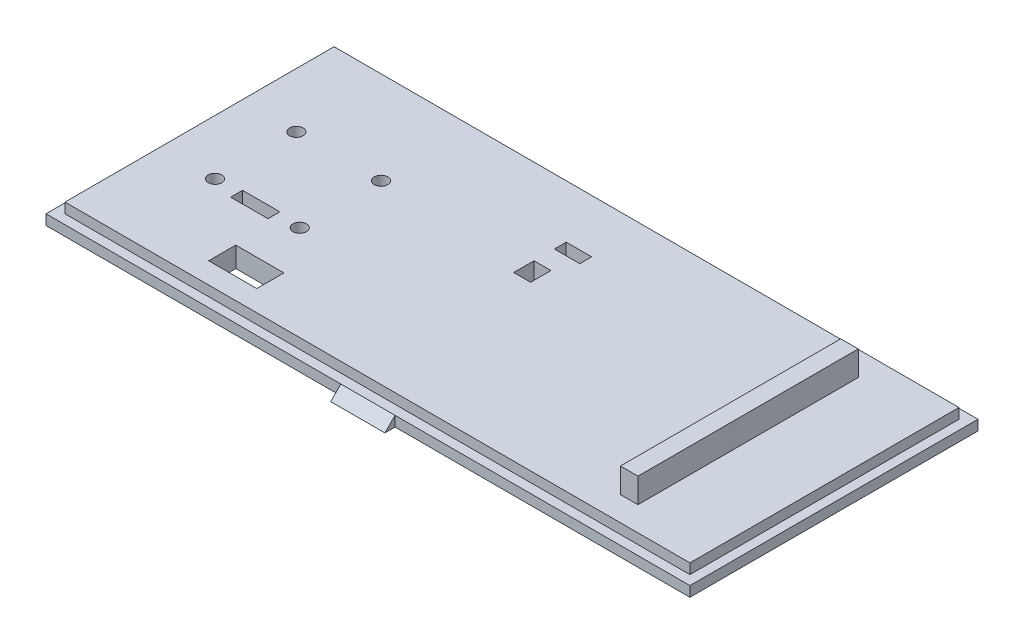
SolidWorks part; units mm, degrees
ref_plane "Front Plane" through (0, 0, 0) normal (0, 0, 1) x (1, 0, 0)
ref_plane "Top Plane" through (0, 0, 0) normal (0, 1, 0) x (1, 0, 0)
ref_plane "Right Plane" through (0, 0, 0) normal (1, 0, 0) x (0, 0, -1)
sketch "Sketch2" plane through (0, 0, 0) normal (0, 1, 0) x (1, 0, 0)
  line L1 (0, 0) -> (-190, 0)
  line L2 (0, 0) -> (0, 85)
  line L3 (0, 85) -> (-190, 85)
  line L4 (-190, 0) -> (-190, 85)
extrude "Boss-Extrude1" add sketch "Sketch2" along normal blind 3
sketch "Sketch6" plane through (0, 3, 0) normal (0, 1, 0) x (1, 0, 0)
  line L0 (-190, 85) -> (-190, 0) construction
  line L1 (-187.2, 82.2) -> (-2.8, 82.2)
  line L2 (-187.2, 82.2) -> (-187.2, 2.8)
  line L3 (-187.2, 2.8) -> (-2.8, 2.8)
  line L4 (-2.8, 82.2) -> (-2.8, 2.8)
  line L5 (0, 85) -> (-190, 85) construction
  line L6 (-55, 0) -> (55, 0) construction
  line L7 (0, -55) -> (0, 55) construction
  dimension "D1" = 2.8
  dimension "D2" = 2.8
  dimension "D3" = 2.8
  dimension "D4" = 2.8
extrude "Boss-Extrude4" add sketch "Sketch6" along normal blind 3
sketch "Sketch8" plane through (0, 3, 0) normal (0, 1, 0) x (1, 0, 0)
  line L0 (-95, 0) -> (-95, 85) construction
  line L1 (-190, 0) -> (0, 0) construction
  line L2 (0, 85) -> (-190, 85) construction
  line L3 (-190, 42.5) -> (0, 42.5) construction
  line L4 (-87, 0) -> (-103, 0)
  line L5 (-95, 0) -> (-95, -3)
  line L6 (-87, -3) -> (-103, -3)
  line L7 (-103, 0) -> (-103, -3)
  line L8 (-190, 85) -> (-190, 0) construction
  line L9 (0, 0) -> (0, 85) construction
  line L10 (-87, 0) -> (-87, -3)
  line L11 (-87, 85) -> (-87, 88)
  line L12 (-87, 85) -> (-103, 85)
  line L13 (-103, 85) -> (-103, 88)
  line L14 (-87, 88) -> (-103, 88)
  dimension "D1" = 8
  dimension "D2" = 3
extrude "Boss-Extrude5" add sketch "Sketch8" against normal blind 3 contours L4 L7 L6 L10 | L14 L13 L12 L11
chamfer "Chamfer2" distance 3 angle 45 2 edges at (-95, 3, 3) (-95, 3, -88)
sketch "Sketch10" plane through (0, 0, 0) normal (0, -1, 0) x (1, 0, 0)
  line L0 (-190, -85) -> (-190, 0) construction
  line L1 (-103, -63) -> (-95.5, -63)
  line L2 (-103, -63) -> (-103, -66.5)
  line L3 (-103, -66.5) -> (-95.5, -66.5)
  line L4 (-95.5, -63) -> (-95.5, -66.5)
  line L5 (-190, 0) -> (-103, 0) construction
  line L6 (-103, -85) -> (-190, -85) construction
  dimension "D1" = 87
  dimension "D2" = 7.5
  dimension "D3" = 3.5
  dimension "D4" = 63
  dimension "D5" = 18.5
extrude "Cut-Extrude1" cut sketch "Sketch10" against normal through all and the other way through all
sketch "Sketch11" plane through (0, 0, 0) normal (0, -1, 0) x (1, 0, 0)
  line L1 (-103, -51) -> (-98, -51)
  line L2 (-103, -51) -> (-103, -57)
  line L3 (-103, -57) -> (-98, -57)
  line L4 (-98, -51) -> (-98, -57)
  line L5 (-190, -85) -> (-190, 0) construction
  line L6 (-103, -63) -> (-95.5, -63) construction
  dimension "D1" = 6
  dimension "D2" = 87
  dimension "D3" = 6
  dimension "D4" = 5
extrude "Cut-Extrude2" cut sketch "Sketch11" against normal through all
sketch "Sketch12" plane through (0, 0, 0) normal (0, -1, 0) x (1, 0, 0)
  line L0 (-190, -85) -> (-190, 0) construction
  line L1 (-164, -32) -> (-153, -32)
  line L2 (-164, -32) -> (-164, -28.5)
  line L3 (-164, -28.5) -> (-153, -28.5)
  line L4 (-153, -32) -> (-153, -28.5)
  line L5 (-190, 0) -> (-103, 0) construction
  line L6 (-158.5, -32) -> (-158.5, 15.5771) construction
  line L7 (-171, -54.8755) -> (-171, 0) construction
  line L8 (-103, -85) -> (-190, -85) construction
  circle A0 centre (-171, -54.8755) radius 2
  circle A1 centre (-171, -30.8755) radius 2
  circle A2 centre (-146, -54.8755) radius 2
  circle A3 centre (-146, -30.8755) radius 2
  dimension "D5" = 7
  dimension "D6" = 24
  dimension "D1" = 26
  dimension "D2" = 32
  dimension "D3" = 3.5
  dimension "D4" = 11
  dimension "D7" = 53
extrude "Cut-Extrude3" cut sketch "Sketch12" against normal through all
sketch "Sketch13" plane through (0, 0, 0) normal (0, -1, 0) x (1, 0, 0)
  line L0 (-190, -85) -> (-190, 0) construction
  line L1 (-151, -9) -> (-136.8, -9)
  line L2 (-151, -9) -> (-151, -17)
  line L3 (-151, -17) -> (-136.8, -17)
  line L4 (-136.8, -9) -> (-136.8, -17)
  line L6 (-103, -85) -> (-190, -85) construction
  dimension "D1" = 39
  dimension "D2" = 68
  dimension "D3" = 14.2
  dimension "D4" = 8
extrude "Cut-Extrude4" cut sketch "Sketch13" against normal through all
sketch "Sketch14" plane through (0, 6, 0) normal (0, 1, 0) x (1, 0, 0)
  line L0 (-51.8, 2.8) -> (-51.8, 82.2)
  line L1 (-187.2, 2.8) -> (-2.8, 2.8) construction
  line L2 (-2.8, 82.2) -> (-187.2, 82.2) construction
  line L3 (-2.8, 2.8) -> (-2.8, 82.2) construction
  line L4 (-51.8, 42.5) -> (-2.8, 42.5) construction
  line L5 (-28.0054, 82.2) -> (-28.0054, 2.8) construction
  line L6 (-2.8, 82.2) -> (-187.2, 82.2) construction
  line L7 (-2.8, 2.8) -> (-2.8, 82.2) construction
  line L8 (-187.2, 2.8) -> (-2.8, 2.8) construction
  line L9 (-30.5054, 8) -> (-25.5054, 8)
  line L10 (-30.5054, 8) -> (-30.5054, 2.8)
  line L11 (-30.5054, 2.8) -> (-25.5054, 2.8)
  line L12 (-25.5054, 8) -> (-25.5054, 2.8)
  line L13 (-30.5054, 82.2) -> (-25.5054, 82.2)
  line L14 (-25.5054, 77) -> (-25.5054, 82.2)
  line L15 (-30.5054, 77) -> (-30.5054, 82.2)
  line L16 (-30.5054, 77) -> (-25.5054, 77)
  line L17 (-30.5054, 75) -> (-25.3317, 75)
  line L18 (-30.5054, 10) -> (-25.3317, 10)
  line L19 (-30.5054, 10) -> (-30.5054, 75)
  line L20 (-30.5054, 42.5) -> (-25.3317, 42.5)
  line L21 (-25.3317, 10) -> (-25.3317, 75)
  dimension "D1" = 49
  dimension "D2" = 2.5
  dimension "D3" = 2.5
  dimension "D4" = 69
  dimension "D6" = 2
extrude "Boss-Extrude6" add sketch "Sketch14" along normal blind 7.3 contours L19 L17 L21 L18
